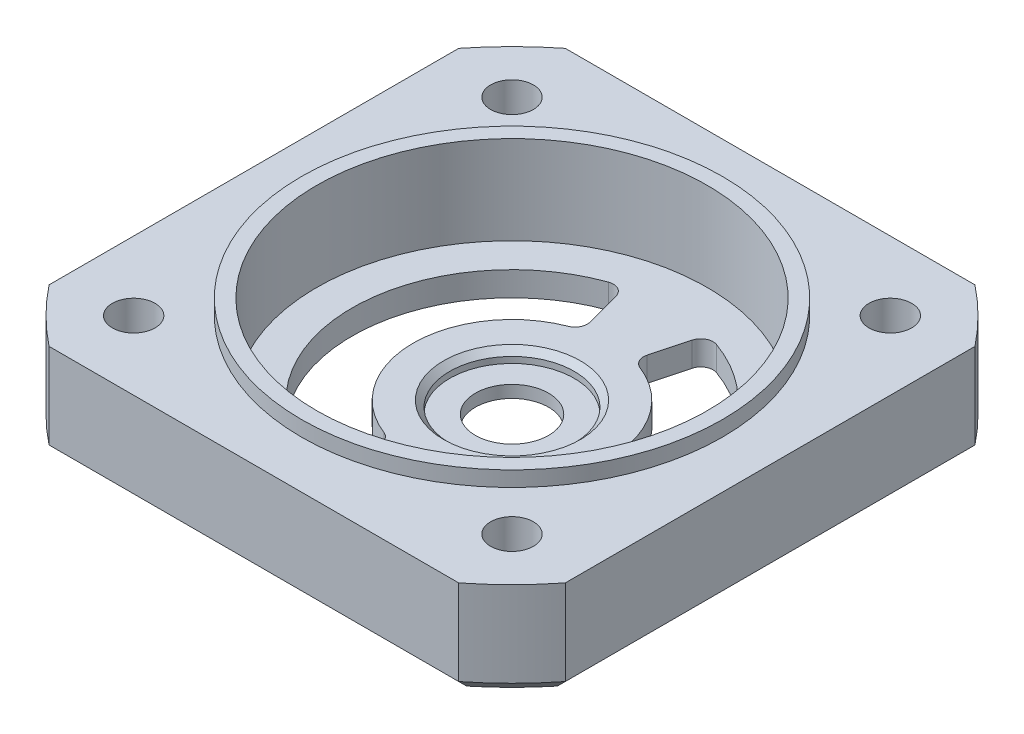
SolidWorks part; units mm, degrees
ref_plane "Front Plane" through (0, 0, 0) normal (0, 0, 1) x (1, 0, 0)
ref_plane "Top Plane" through (0, 0, 0) normal (0, 1, 0) x (1, 0, 0)
ref_plane "Right Plane" through (0, 0, 0) normal (1, 0, 0) x (0, 0, -1)
sketch "Sketch2" plane through (0, 0, 0) normal (0, 1, 0) x (1, 0, 0)
  line L1 (-21.15, 21.15) -> (21.15, 21.15)
  line L2 (-21.15, 21.15) -> (-21.15, -21.15)
  line L3 (-21.15, -21.15) -> (21.15, -21.15)
  line L4 (21.15, 21.15) -> (21.15, -21.15)
  line L5 (-21.15, 21.15) -> (21.15, -21.15) construction
  line L6 (-21.15, -21.15) -> (21.15, 21.15) construction
  point P0 (0, 0)
  dimension "D1" = 42.3
extrude "Boss-Extrude1" add sketch "Sketch2" along normal blind 8
sketch "Sketch5" plane through (0, 8, 0) normal (0, 1, 0) x (1, 0, 0)
  circle A0 centre (0, 0) radius 27
  circle A1 centre (0, 0) radius 29.9106
  dimension "D1" = 54
extrude "Cut-Extrude4" cut sketch "Sketch5" against normal through all
sketch "Sketch6" plane through (0, 8, 0) normal (0, 1, 0) x (1, 0, 0)
  circle A2 centre (0, 0) radius 16
  circle A3 centre (0, 0) radius 10 construction
  dimension "D1" = 32
  dimension "D5" = 20
extrude "Cut-Extrude7" cut sketch "Sketch6" against normal offset from surface (7 mm away) 1 up to face at (0, 0, 0)
sketch "Sketch8" plane through (0, 1, 0) normal (0, 1, 0) x (1, 0, 0)
  circle A0 centre (0, 0) radius 5.1
  circle A2 centre (0, 0) radius 16
  circle A3 centre (0, 0) radius 16
  dimension "D1" = 10.2
  dimension "D2" = 0
extrude "Boss-Extrude3" add sketch "Sketch8" along normal blind 1
sketch "Sketch9" plane through (0, 2, 0) normal (0, 1, 0) x (1, 0, 0)
  line L0 (3.3905, 12.6536) -> (2.0964, 7.824)
  line L1 (3.3905, -12.6536) -> (2.0964, -7.824)
  line L2 (2.0964, -7.824) -> (0, 0) construction
  line L3 (2.0964, 7.824) -> (0, 0) construction
  line L4 (-21.15, 16.7833) -> (-21.15, -16.7833) construction
  line L5 (0, -4.4) -> (0, 4.4) construction
  line L6 (-2.0964, 7.824) -> (0, 0) construction
  line L7 (-2.0964, -7.824) -> (0, 0) construction
  line L8 (-3.3905, -12.6536) -> (-2.0964, -7.824)
  line L9 (-3.3905, 12.6536) -> (-2.0964, 7.824)
  arc A0 (3.3905, 12.6536) -> (3.3905, -12.6536) centre (0, 0) cw
  circle A1 centre (0, 0) radius 5.1 construction
  arc A2 (2.0964, 7.824) -> (2.0964, -7.824) centre (0, 0) cw
  arc A3 (-2.0964, 7.824) -> (-2.0964, -7.824) centre (0, 0) ccw
  arc A4 (-3.3905, 12.6536) -> (-3.3905, -12.6536) centre (0, 0) ccw
  dimension "D1" = 15
  dimension "D4" = 3
  dimension "D2" = 15
  dimension "D3" = 5
extrude "Cut-Extrude8" cut sketch "Sketch9" against normal through all
fillet "Fillet1" radius 1 8 edges at (-3.3905, 1, 12.6536) (-2.0964, 1, -7.824) (-2.0964, 1, 7.824) (-3.3905, 1, -12.6536) (2.0964, 1, 7.824) (2.0964, 1, -7.824) (3.3905, 1, 12.6536) (3.3905, 1, -12.6536)
sketch "Sketch10" plane through (0, 1, 0) normal (0, 1, 0) x (1, 0, 0)
  circle A0 centre (0, 0) radius 3
  dimension "D1" = 6
extrude "Cut-Extrude9" cut sketch "Sketch10" against normal through all
sketch "Sketch7" plane through (0, 8, 0) normal (0, 1, 0) x (1, 0, 0)
  line L1 (-15.5, 15.5) -> (15.5, 15.5) construction
  line L2 (-15.5, 15.5) -> (-15.5, -15.5) construction
  line L3 (-15.5, -15.5) -> (15.5, -15.5) construction
  line L4 (15.5, 15.5) -> (15.5, -15.5) construction
  line L5 (-15.5, 15.5) -> (15.5, -15.5) construction
  line L6 (-15.5, -15.5) -> (15.5, 15.5) construction
  circle A0 centre (-15.5, 15.5) radius 1.75
  circle A1 centre (15.5, 15.5) radius 1.75
  circle A2 centre (15.5, -15.5) radius 1.75
  circle A3 centre (-15.5, -15.5) radius 1.75
  point P0 (0, 0)
  point P16 (0, 0)
  dimension "D3" = 3.5
  dimension "D1" = 31
  dimension "D2" = 31
  dimension "D4" = 4
extrude "Cut-Extrude6" cut sketch "Sketch7" against normal through all
chamfer "Chamfer4" distance 1 angle 45 8 edges at (19.0919, 0, 19.0919) (0, 0, 21.15) (-19.0919, 0, 19.0919) (-21.15, 0, 0) (-19.0919, 0, -19.0919) (0, 0, -21.15) (19.0919, 0, -19.0919) (21.15, 0, 0)
chamfer "Chamfer5" distance 2 angle 45 4 edges at (-15.5, 0, -13.75) (15.5, 0, -13.75) (15.5, 0, 17.25) (-15.5, 0, 17.25)
chamfer "Chamfer6" distance 0.5 angle 45 1 edges at (0, 2, 5.1)
sketch "Sketch11" plane through (0, 8, 0) normal (0, 1, 0) x (1, 0, 0)
  circle A0 centre (0, 0) radius 17.25
  circle A1 centre (0, 0) radius 16 construction
  circle A2 centre (0, 0) radius 16
  dimension "D1" = 1.25
extrude "Boss-Extrude4" add sketch "Sketch11" along normal blind 1.25
